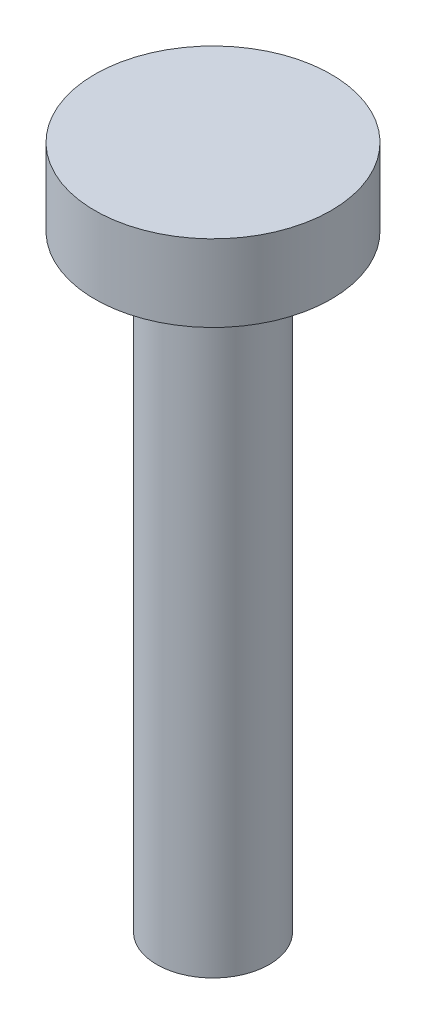
SolidWorks part; units mm, degrees
material "Brass"
ref_plane "Front Plane" through (0, 0, 0) normal (0, 0, 1) x (1, 0, 0)
ref_plane "Top Plane" through (0, 0, 0) normal (0, 1, 0) x (1, 0, 0)
ref_plane "Right Plane" through (0, 0, 0) normal (1, 0, 0) x (0, 0, -1)
sketch "Sketch1" plane through (0, 0, 0) normal (0, 0, 1) x (1, 0, 0)
  line L0 (0, 0) -> (0, 57.9) construction
  line L1 (0, 0) -> (4.7625, 0)
  line L2 (4.7625, 0) -> (4.7625, 51.4)
  line L3 (4.7625, 51.4) -> (10, 51.4)
  line L4 (10, 51.4) -> (10, 57.9)
  line L5 (10, 57.9) -> (0, 57.9)
  line L6 (0, 57.9) -> (0, 0)
revolve "Revolve1" add sketch "Sketch1" angle 360 about L0
